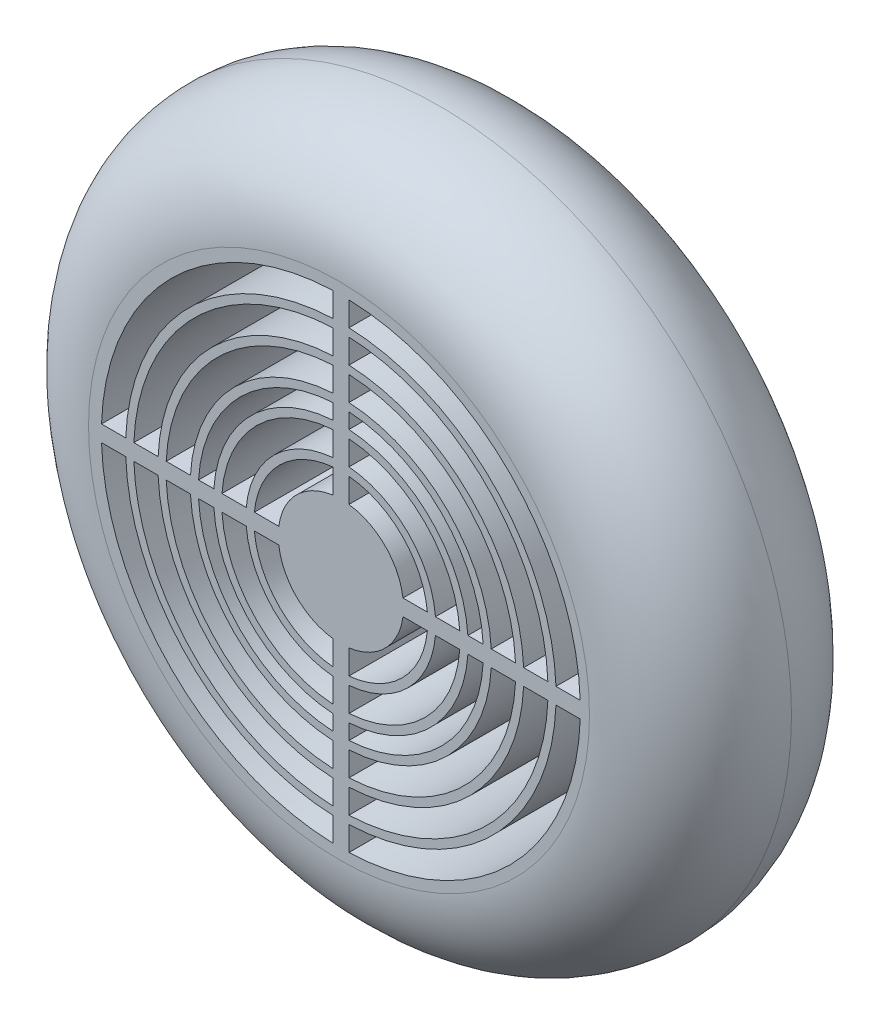
SolidWorks part; units mm, degrees
ref_plane "Alzado" through (0, 0, 0) normal (0, 0, 1) x (1, 0, 0)
ref_plane "Planta" through (0, 0, 0) normal (0, 1, 0) x (1, 0, 0)
ref_plane "Vista lateral" through (0, 0, 0) normal (1, 0, 0) x (0, 0, -1)
sketch "Croquis1" plane through (0, 0, 0) normal (0, 0, 1) x (1, 0, 0)
  circle A0 centre (-1.154, 0) radius 217.5
  dimension "D1" = 435
extrude "Saliente-Extruir1" add sketch "Croquis1" along normal blind 125
fillet "Redondeo2" radius 62.5 2 edges at (216.346, 0, 125) (216.346, 0, 0)
sketch "Croquis6" plane through (0, 0, 125) normal (0, 0, 1) x (1, 0, 0)
  line L0 (-5, 216.2436) -> (-5, -216.2436)
  line L1 (5, 216.2436) -> (5, -216.2436)
  line L2 (-216.2436, 5) -> (216.2436, 5)
  line L3 (216.2436, -5) -> (-216.2436, -5)
  circle A1 centre (0, 0) radius 13.7534
  circle A2 centre (0, 0) radius 18.7534
  circle A3 centre (0, 0) radius 33.7534
  circle A4 centre (0, 0) radius 38.7534
  circle A5 centre (0, 0) radius 73.7534
  circle A6 centre (0, 0) radius 78.7534
  circle A7 centre (0, 0) radius 108.2001
  circle A8 centre (0, 0) radius 113.2001
  circle A9 centre (0, 0) radius 148.2001
  circle A10 centre (0, 0) radius 153.2001
  circle A11 centre (0, 0) radius 53.7534
  circle A12 centre (0, 0) radius 58.7534
  circle A13 centre (0, 0) radius 88.2001
  circle A14 centre (0, 0) radius 93.2001
  circle A15 centre (0, 0) radius 128.2001
  circle A16 centre (0, 0) radius 133.2001
  circle A17 centre (0, 0) radius 216.3014
  dimension "D1" = 5
  dimension "D2" = 5
  dimension "D3" = 5
  dimension "D4" = 5
  dimension "D5" = 5
  dimension "D6" = 15
  dimension "D7" = 9.4467
  dimension "D8" = 15
  dimension "D9" = 5
  dimension "D10" = 5
  dimension "D11" = 15
  dimension "D12" = 15
  dimension "D13" = 5
  dimension "D14" = 15
  dimension "D15" = 15
  dimension "D16" = 10
  dimension "D17" = 5
  dimension "D18" = 5
  dimension "D19" = 10
extrude "Cortar-Extruir4" cut sketch "Croquis6" against normal blind 115 contours A16 L2 A9 L1 | A16 L1 A9 L3 | A16 L3 A9 L0 | A16 L0 A9 L2 | L0 A15 L2 A8 | L3 A15 L0 A8 | A14 L0 A7 L2 | A14 L3 A7 L0 | A12 L3 A5 L0 | A12 L0 A5 L2 | L0 A13 L2 A6 | L3 A13 L0 A6 | L3 A11 L0 A4 | L0 A11 L2 A4 | L1 A11 L3 A4 | L2 A11 L1 A4 | A12 L2 A5 L1 | L2 A13 L1 A6 | A14 L2 A7 L1 | L2 A15 L1 A8 | L1 A15 L3 A8 | A14 L1 A7 L3 | L1 A13 L3 A6 | A12 L1 A5 L3 region at (-7.024, 140.611, 125) region at (103.3621, 103.3621, 125) region at (-6.7409, 120.5961, 125) region at (-140.611, -7.024, 125) region at (89.4201, 89.4201, 125) region at (-6.4578, 100.5752, 125) region at (-120.5961, -6.7409, 125) region at (103.3621, -103.3621, 125) region at (75.4782, 75.4782, 125) region at (-6.1746, 83.3264, 125) region at (-100.5752, -6.4578, 125) region at (89.4201, -89.4201, 125) region at (61.5363, 61.5363, 125) region at (-43.2111, 43.2111, 125) region at (-83.3264, -6.1746, 125) region at (75.4782, -75.4782, 125) region at (43.2111, 43.2111, 125) region at (-30.5634, 30.5634, 125) region at (-43.2111, -43.2111, 125) region at (61.5363, -61.5363, 125) region at (30.5634, 30.5634, 125) region at (-30.5634, -30.5634, 125) region at (43.2111, -43.2111, 125) region at (30.5634, -30.5634, 125)
sketch "Croquis7" plane through (-5, 0, 0) normal (-1, 0, 0) x (0, 0, 1)
  line L0 (10, 128.1026) -> (125, 128.1026) construction
  line L1 (124.0875, 133.1062) -> (10, 133.1062)
  line L5 (124.0875, 113.0896) -> (10, 113.0896)
  line L7 (124.0875, 128.1026) -> (10, 128.1026)
  line L9 (10, 128.1026) -> (10, 113.0896) construction
  line L10 (62.5, 26.8003) -> (62.5, 159.5869) construction
  line L11 (10, 108.0845) -> (124.0875, 108.0845)
  line L13 (10, 93.0659) -> (124.0875, 93.0659)
  line L15 (10, 88.0583) -> (124.0875, 88.0583)
  line L17 (10, 78.5946) -> (124.0875, 78.5946)
  line L19 (10, 73.5838) -> (124.0875, 73.5838)
  line L21 (10, 58.5403) -> (124.0875, 58.5403)
  line L25 (124.0875, 53.5204) -> (10, 53.5204)
  line L27 (62.5, 217.5) -> (62.5, -217.5) construction
  line L28 (0, 0) -> (148.2485, 0) construction
  line L35 (124.0875, 58.5403) -> (124.0875, 53.5204)
  line L36 (124.0875, 78.5946) -> (124.0875, 73.5838)
  line L37 (124.0875, 93.0659) -> (124.0875, 88.0583)
  line L38 (124.0875, 113.0896) -> (124.0875, 108.0845)
  line L39 (124.0875, 133.1062) -> (124.0875, 128.1026)
  line L40 (10, 133.1062) -> (10, 128.1026)
  line L41 (10, 113.0896) -> (10, 108.0845)
  line L42 (10, 93.0659) -> (10, 88.0583)
  line L43 (10, 78.5946) -> (10, 73.5838)
  line L44 (10, 58.5403) -> (10, 53.5204)
